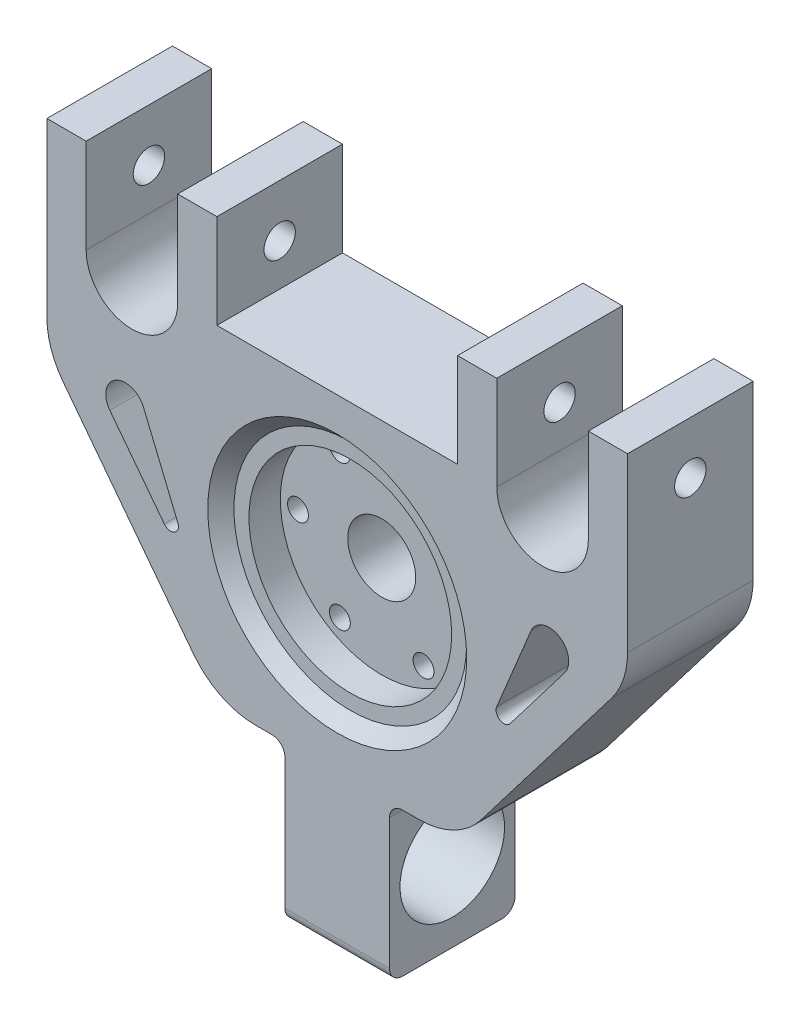
SolidWorks part; units mm, degrees
material "7075-O (SS)"
ref_plane "Płaszczyzna przednia" through (0, 0, 0) normal (0, 0, 1) x (1, 0, 0)
ref_plane "Płaszczyzna górna" through (0, 0, 0) normal (0, 1, 0) x (1, 0, 0)
ref_plane "Płaszczyzna prawa" through (0, 0, 0) normal (1, 0, 0) x (0, 0, -1)
sketch "Szkic1" plane through (0, 0, 0) normal (0, 0, 1) x (1, 0, 0)
  line L1 (-111, -62.5) -> (111, -62.5)
  line L2 (-111, -62.5) -> (-111, 62.5)
  line L3 (-111, 62.5) -> (111, 62.5)
  line L4 (111, -62.5) -> (111, 62.5)
  line L5 (-111, -62.5) -> (111, 62.5) construction
  line L6 (-111, 62.5) -> (111, -62.5) construction
  circle A0 centre (0, 0) radius 13
  circle A1 centre (-32, 0) radius 4
  circle A2 centre (-16, 27.7128) radius 4
  circle A3 centre (16, 27.7128) radius 4
  circle A4 centre (32, 0) radius 4
  circle A5 centre (16, -27.7128) radius 4
  circle A6 centre (-16, -27.7128) radius 4
  point P0 (0, 0)
  point P22 (0, 0)
  point P23 (0, 0)
  dimension "D3" = 26
  dimension "D4" = 8
  dimension "D5" = 32
  dimension "D2" = 222
  dimension "12" = 125
  dimension "D9" = 32
  dimension "D6" = 6
extrude "Dodanie-wyciągnięcie1" add sketch "Szkic1" along normal blind 13.5 and the other way blind 13.5
sketch "Szkic4" plane through (0, 62.5, 0) normal (0, 1, 0) x (1, 0, 0)
  line L0 (111, -13.5) -> (-111, -13.5) construction
  line L1 (-111, 13.5) -> (-96, 13.5)
  line L2 (-111, 13.5) -> (-111, -13.5)
  line L3 (-111, -13.5) -> (-96, -13.5)
  line L4 (-96, 13.5) -> (-96, -13.5)
  line L5 (111, 13.5) -> (-111, 13.5) construction
  line L6 (-61, 13.5) -> (-46, 13.5)
  line L7 (-61, 13.5) -> (-61, -13.5)
  line L8 (-61, -13.5) -> (-46, -13.5)
  line L9 (-46, 13.5) -> (-46, -13.5)
  line L11 (46, 13.5) -> (61, 13.5)
  line L12 (46, 13.5) -> (46, -13.5)
  line L13 (46, -13.5) -> (61, -13.5)
  line L14 (61, 13.5) -> (61, -13.5)
  line L15 (111, 13.5) -> (96, 13.5)
  line L16 (111, 13.5) -> (111, -13.5)
  line L17 (111, -13.5) -> (96, -13.5)
  line L18 (96, 13.5) -> (96, -13.5)
  dimension "D1" = 15
  dimension "D2" = 15
  dimension "D3" = 15
  dimension "D4" = 15
  dimension "D5" = 35
  dimension "D6" = 35
extrude "Dodanie-wyciągnięcie4" add sketch "Szkic4" along normal blind 36
sketch "Szkic13" plane through (0, 0, 13.5) normal (0, 0, 1) x (1, 0, 0)
  circle A0 centre (0, 0) radius 38.75
  circle A1 centre (0, 0) radius 13 construction
  dimension "D1" = 77.5
extrude "Wytnij-wyciągnięcie4" cut sketch "Szkic13" against normal blind 17 contours A0
sketch "Szkic15" plane through (0, 0, 13.5) normal (0, 0, 1) x (1, 0, 0)
  circle A0 centre (0, 0) radius 44.5
  circle A1 centre (0, 0) radius 38.75 construction
  dimension "D1" = 89
extrude "Wytnij-wyciągnięcie5" cut sketch "Szkic15" against normal blind 5
draft "Pochylenie1" type of draft neutral plane draft angle 45 faces to draft 1 face at (44.5, 0, 8.5) neutral plane through (0, 0, 8.5) neutral plane normal (0, 0, 1) parameters "D1"=45
sketch "Szkic16" plane through (0, 0, -13.5) normal (0, 0, -1) x (-1, 0, 0)
  line L18 (-111, 98.5) -> (-111, -62.5)
  line L19 (-111, -62.5) -> (111, -62.5)
  line L22 (111, -62.5) -> (111, 98.5)
  line L23 (111, 98.5) -> (96, 98.5)
  line L24 (96, 98.5) -> (96, 62.5)
  line L25 (96, 62.5) -> (61, 62.5)
  line L26 (61, 62.5) -> (61, 98.5)
  line L27 (61, 98.5) -> (46, 98.5)
  line L28 (46, 98.5) -> (46, 62.5)
  line L29 (46, 62.5) -> (-46, 62.5)
  line L30 (-46, 62.5) -> (-46, 98.5)
  line L31 (-46, 98.5) -> (-61, 98.5)
  line L32 (-61, 98.5) -> (-61, 62.5)
  line L33 (-61, 62.5) -> (-96, 62.5)
  line L34 (-96, 62.5) -> (-96, 98.5)
  line L35 (-96, 98.5) -> (-111, 98.5)
  line L36 (-111, 98.5) -> (-111, -62.5)
  line L37 (-111, -62.5) -> (111, -62.5)
  line L40 (111, -62.5) -> (111, 98.5)
  line L41 (111, 98.5) -> (96, 98.5)
  line L42 (96, 98.5) -> (96, 62.5)
  line L43 (96, 62.5) -> (61, 62.5)
  line L44 (61, 62.5) -> (61, 98.5)
  line L45 (61, 98.5) -> (46, 98.5)
  line L46 (46, 98.5) -> (46, 62.5)
  line L47 (46, 62.5) -> (-46, 62.5)
  line L48 (-46, 62.5) -> (-46, 98.5)
  line L49 (-46, 98.5) -> (-61, 98.5)
  line L50 (-61, 98.5) -> (-61, 62.5)
  line L51 (-61, 62.5) -> (-96, 62.5)
  line L52 (-96, 62.5) -> (-96, 98.5)
  line L53 (-96, 98.5) -> (-111, 98.5)
  circle A1 centre (0, 0) radius 13
  circle A2 centre (0, 0) radius 13
  circle A3 centre (32, 0) radius 4
  circle A4 centre (32, 0) radius 4
  circle A5 centre (16, 27.7128) radius 4
  circle A6 centre (16, 27.7128) radius 4
  circle A7 centre (-16, 27.7128) radius 4
  circle A8 centre (-16, 27.7128) radius 4
  circle A9 centre (-32, 0) radius 4
  circle A10 centre (-32, 0) radius 4
  circle A11 centre (-16, -27.7128) radius 4
  circle A12 centre (-16, -27.7128) radius 4
  circle A13 centre (16, -27.7128) radius 4
  circle A14 centre (16, -27.7128) radius 4
  dimension "D1" = 0
  dimension "D2" = 0
  dimension "D3" = 0
  dimension "D4" = 0
  dimension "D5" = 0
  dimension "D6" = 0
  dimension "D7" = 0
  dimension "D8" = 0
extrude "Dodanie-wyciągnięcie6" add sketch "Szkic16" along normal blind 21
sketch "Szkic5" plane through (-111, 0, 0) normal (-1, 0, 0) x (0, 0, 1)
  line L0 (13.5, 98.5) -> (13.5, -62.5) construction
  line L2 (-34.5, 98.5) -> (13.5, 98.5) construction
  circle A0 centre (-10.5, 78.5) radius 6
  dimension "D1" = 12
  dimension "D2" = 24
  dimension "D3" = 20
extrude "Wytnij-wyciągnięcie3" cut sketch "Szkic5" against normal through all contours A0
sketch "Szkic18" plane through (0, 0, -34.5) normal (0, 0, -1) x (-1, 0, 0)
  line L2 (111, 22.5) -> (46, -62.5)
  line L3 (111, -62.5) -> (111, 98.5) construction
  line L4 (-111, -62.5) -> (111, -62.5) construction
  line L5 (111, 22.5) -> (111, -62.5)
  line L6 (111, -62.5) -> (46, -62.5)
  line L7 (-111, -62.5) -> (-46, -62.5)
  line L8 (-46, -62.5) -> (-111, 22.5)
  line L9 (-111, 98.5) -> (-111, -62.5) construction
  line L10 (-111, 22.5) -> (-111, -62.5)
  dimension "D1" = 65
  dimension "D2" = 85
extrude "Wytnij-wyciągnięcie6" cut sketch "Szkic18" against normal through all
fillet "Zaokrąglenie1" radius 30 1 edges at (-111, 22.5, -10.5)
fillet "Zaokrąglenie2" radius 30 3 edges at (111, 22.5, -10.5) (46, -62.5, -10.5) (-46, -62.5, -10.5)
sketch "Szkic19" plane through (0, 0, -34.5) normal (0, 0, -1) x (-1, 0, 0)
  line L5 (-31.1748, -62.5) -> (31.1748, -62.5) construction
  line L6 (-20, -62.5) -> (20, -62.5)
  line L7 (-20, -62.5) -> (-20, -122.5)
  line L8 (-20, -122.5) -> (20, -122.5)
  line L9 (20, -62.5) -> (20, -122.5)
  point P4 (0, -62.5)
  dimension "D1" = 40
  dimension "D2" = 60
extrude "Dodanie-wyciągnięcie7" add sketch "Szkic19" against normal up to surface (48 mm away) up to face at (-49.5, 0, 13.5)
sketch "Szkic23" plane through (20, 0, 0) normal (1, 0, 0) x (0, 0, -1)
  line L0 (-13.5, -122.5) -> (34.5, -122.5) construction
  circle A0 centre (10.5, -92.5) radius 20
  point P5 (10.5, -122.5)
  dimension "D1" = 40
  dimension "D2" = 30
extrude "Wytnij-wyciągnięcie7" cut sketch "Szkic23" against normal up to next
sketch "Szkic24" plane through (0, 0, -34.5) normal (0, 0, -1) x (-1, 0, 0)
  line L0 (-96, 62.5) -> (-61, 62.5)
  line L1 (61, 62.5) -> (96, 62.5)
  line L2 (-96, 62.5) -> (-96, 98.5) construction
  line L3 (61, 62.5) -> (61, 98.5) construction
  arc A0 (-96, 62.5) -> (-61, 62.5) centre (-78.5, 62.5) ccw
  arc A1 (61, 62.5) -> (96, 62.5) centre (78.5, 62.5) ccw
extrude "Wytnij-wyciągnięcie8" cut sketch "Szkic24" against normal up to next
fillet "Zaokrąglenie4" radius 5 2 edges at (20, -62.5, -10.5) (-20, -62.5, -10.5)
fillet "Zaokrąglenie5" radius 5 2 edges at (0, -122.5, -34.5) (0, -122.5, 13.5)
sketch "Szkic25" plane through (0, 0, 13.5) normal (0, 0, 1) x (1, 0, 0)
  line L0 (-60.9515, -10.3535) -> (-74.0693, 21.3662)
  line L1 (-66.1069, -13.3224) -> (-86.9577, 13.9441)
  line L2 (0, 0) -> (0, 65.4939) construction
  line L3 (66.1069, -13.3224) -> (86.9577, 13.9441)
  line L4 (-111, 98.5) -> (-111, 32.656) construction
  line L5 (-61, 98.5) -> (-46, 98.5) construction
  line L6 (60.9515, -10.3535) -> (74.0693, 21.3662)
  line L7 (-104.8307, 14.4325) -> (-55.0056, -50.7235) construction
  arc A0 (-74.0693, 21.3662) -> (-86.9577, 13.9441) centre (-81, 18.5) ccw
  arc A13 (-66.1069, -13.3224) -> (-60.9515, -10.3535) centre (-63.7238, -11.5) ccw
  arc A14 (66.1069, -13.3224) -> (60.9515, -10.3535) centre (63.7238, -11.5) cw
  arc A15 (74.0693, 21.3662) -> (86.9577, 13.9441) centre (81, 18.5) cw
  dimension "D1" = 30
  dimension "D2" = 80
  dimension "D6" = 6
  dimension "D5" = 15
  dimension "D4" = 110
extrude "Wytnij-wyciągnięcie9" cut sketch "Szkic25" against normal up to surface (48 mm away) up to face at (0, 17.7221, -34.5)
